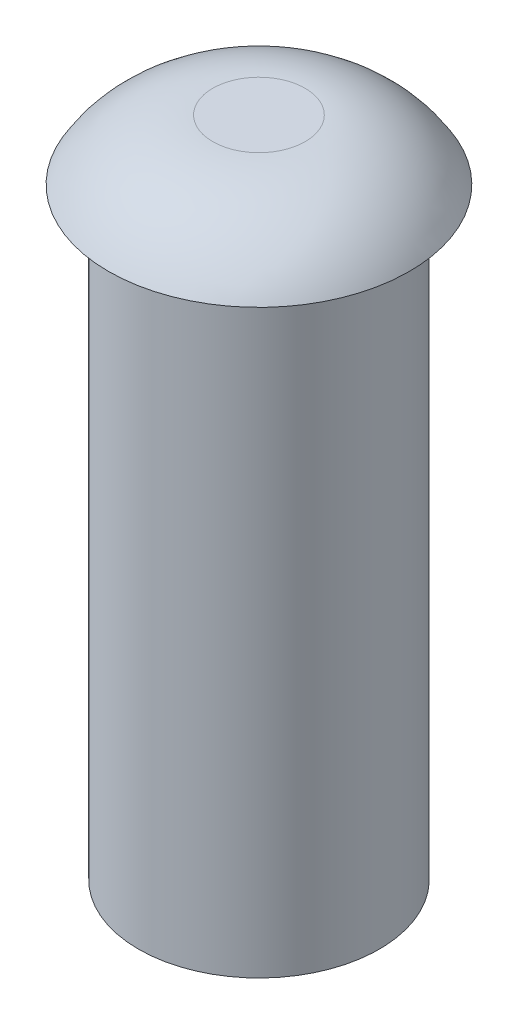
SolidWorks part; units mm, degrees
ref_plane "Front Plane" through (0, 0, 0) normal (0, 0, 1) x (1, 0, 0)
ref_plane "Top Plane" through (0, 0, 0) normal (0, 1, 0) x (1, 0, 0)
ref_plane "Right Plane" through (0, 0, 0) normal (1, 0, 0) x (0, 0, -1)
sketch "Sketch1" plane through (0, 0, 0) normal (0, 1, 0) x (1, 0, 0)
  circle A0 centre (0, 0) radius 1
extrude "Boss-Extrude1" add sketch "Sketch1" along normal blind 5
sketch "Sketch2" plane through (0, 5, 0) normal (0, 1, 0) x (1, 0, 0)
  circle A0 centre (0, 0) radius 1.25
extrude "Boss-Extrude2" add sketch "Sketch2" along normal blind 0.5
fillet "Fillet2" radius 1 1 edges at (0, 5.5, 1.25)
